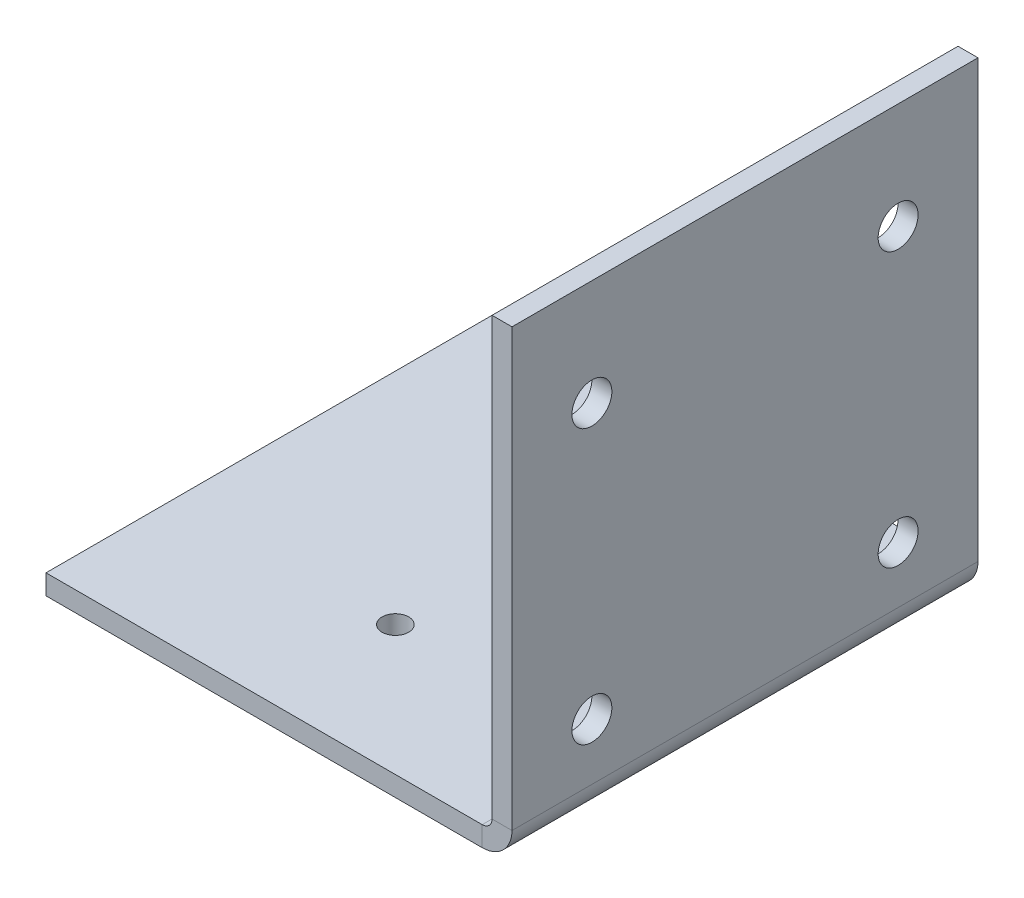
SolidWorks part; units mm, degrees
note: The reader was unsure of these and kept them because the rebuilt part matched: flange length of "Edge-Flange1".
ref_plane "Front Plane" through (0, 0, 0) normal (0, 0, 1) x (1, 0, 0)
ref_plane "Top Plane" through (0, 0, 0) normal (0, 1, 0) x (1, 0, 0)
ref_plane "Right Plane" through (0, 0, 0) normal (1, 0, 0) x (0, 0, -1)
sketch "Sketch1" plane through (0, 12.1009, 0) normal (0, 1, 0) x (1, 0, 0)
  line L0 (-79, -17.5) -> (-79, 17.5)
  line L2 (-79, 17.5) -> (-114, 17.5)
  line L5 (-79, -17.5) -> (-114, -17.5)
  line L6 (-114, 17.5) -> (-114, -17.5)
  dimension "D1" = 35
  dimension "D2" = 35
base flange "Base-Flange1" sketch "Sketch1" thickness 1.5 reverse thickness direction yes parameters "D1"=0.7366
edge flange "Edge-Flange1" sketch "Sketch8" flange angle 90 flange length 35 flange position material inside bend radius 0.7366 thickness 1.5 relief rectangular parameters "D6"=10
sketch "Sketch8" plane through (-79, 13.6009, 0) normal (1, 0, 0) x (0, 0, -1)
  line L2 (-17.5, 0) -> (-17.5, 33.5)
  line L3 (-17.5, 33.5) -> (17.5, 33.5)
  line L4 (17.5, 33.5) -> (17.5, 0)
  line L7 (-17.5, 0) -> (17.5, 0) construction
  line L8 (-17.5, 0) -> (17.5, 0)
bend "EdgeBend1" bend radius 0.7366 bend angle 90 parameters "D5"=1
sketch "Sketch9" plane through (-80.5, 0, 0) normal (-1, 0, 0) x (0, 0, 1)
  line L4 (0, 39.145) -> (0, 15.3511) construction
  line L5 (-11.5, 28.862) -> (14.1325, 28.862) construction
  circle A0 centre (-11.5, 39.145) radius 1.5
  circle A1 centre (11.5, 39.145) radius 1.5
  circle A2 centre (11.5, 18.5789) radius 1.5
  circle A3 centre (-11.5, 18.5789) radius 1.5
  dimension "D1" = 3
  dimension "D2" = 11.5
  dimension "D3" = 10.283
extrude "Cut-Extrude1" cut sketch "Sketch9" against normal up to next normal cut yes
sketch "Sketch10" plane through (0, 12.1009, 0) normal (0, -1, 0) x (1, 0, 0)
  circle A0 centre (-97.5126, -7.747) radius 1
  circle A1 centre (-97.5126, 7.747) radius 1
  point P0 (-97.5126, 7.747)
  point P1 (-97.5126, -7.747)
  dimension "D1" = 2
  dimension "D2" = 2
extrude "Cut-Extrude2" cut sketch "Sketch10" against normal up to next normal cut yes
sketch "Bend-Lines1" [suppressed] plane through (0, 0, 0) normal (0, 1, 0) x (1, 0, 0)
sketch "Bounding-Box1" [suppressed] plane through (0, 0, 0) normal (0, 1, 0) x (1, 0, 0)
sheet metal parameters "Sheet-Metal1" thickness 1.5 parameters "D1"=0.7366
flat pattern "Flat-Pattern1" [suppressed]
sketch "Bend-Lines2" plane through (0, 0, 0) normal (0, 1, 0) x (1, 0, 0)
sketch3d "Bounding-Box2" [suppressed]
  line L0 (-114, -17.5, 0) -> (-114, 17.5, 0) construction
  line L1 (-79, -17.5, 0) -> (-79, 17.5, 0) construction
  line L2 (-114, -17.5, 0) -> (-79, -17.5, 0) construction
  line L3 (-114, 17.5, 0) -> (-79, 17.5, 0) construction
sheet metal parameters "Sheet-Metal2" thickness 1.5 parameters "D1"=0.7366
flat pattern "Flat-Pattern1"
sketch "Bend-Lines2" plane through (0, 10.145, 0) normal (0, -1, 0) x (-1, 0, 0)
  line L0 (80.069, 17.5) -> (80.069, -17.5) construction
  line L1 (80.069, 17.5) -> (80.069, -17.5) construction
sketch3d "Bounding-Box2" [suppressed]
  line L0 (46.1381, 17.5, 0) -> (114, 17.5, 0) construction
  line L1 (46.1381, -17.5, 0) -> (114, -17.5, 0) construction
  line L2 (46.1381, 17.5, 0) -> (46.1381, -17.5, 0) construction
  line L3 (114, 17.5, 0) -> (114, -17.5, 0) construction
bend of the flat pattern "Flatten-<EdgeBend1>1"
sheet metal parameters "Sheet-Metal3" thickness 1.5 parameters "D1"=0.7366
flat pattern "Flat-Pattern1"
sketch "Bend-Lines2" plane through (0, 10.145, 0) normal (0, -1, 0) x (-1, 0, 0)
  line L0 (80.069, 17.5) -> (80.069, -17.5) construction
  line L1 (80.069, 17.5) -> (80.069, -17.5) construction
sketch3d "Bounding-Box2" [suppressed]
  line L0 (46.1381, 17.5, 0) -> (114, 17.5, 0) construction
  line L1 (46.1381, -17.5, 0) -> (114, -17.5, 0) construction
  line L2 (46.1381, 17.5, 0) -> (46.1381, -17.5, 0) construction
  line L3 (114, 17.5, 0) -> (114, -17.5, 0) construction
bend of the flat pattern "Flatten-<EdgeBend1>1"
sheet metal parameters "Sheet-Metal4" thickness 1.5 parameters "D1"=0.7366
flat pattern "Flat-Pattern1"
sketch "Bend-Lines2" plane through (0, 12.1009, 0) normal (0, -1, 0) x (-1, 0, 0)
  line L0 (80.069, 17.5) -> (80.069, -17.5) construction
  line L1 (80.069, 17.5) -> (80.069, -17.5) construction
sketch3d "Bounding-Box2" [suppressed]
  line L0 (46.1381, 17.5, 0) -> (114, 17.5, 0) construction
  line L1 (46.1381, -17.5, 0) -> (114, -17.5, 0) construction
  line L2 (46.1381, 17.5, 0) -> (46.1381, -17.5, 0) construction
  line L3 (114, 17.5, 0) -> (114, -17.5, 0) construction
bend of the flat pattern "Flatten-<EdgeBend1>1"
